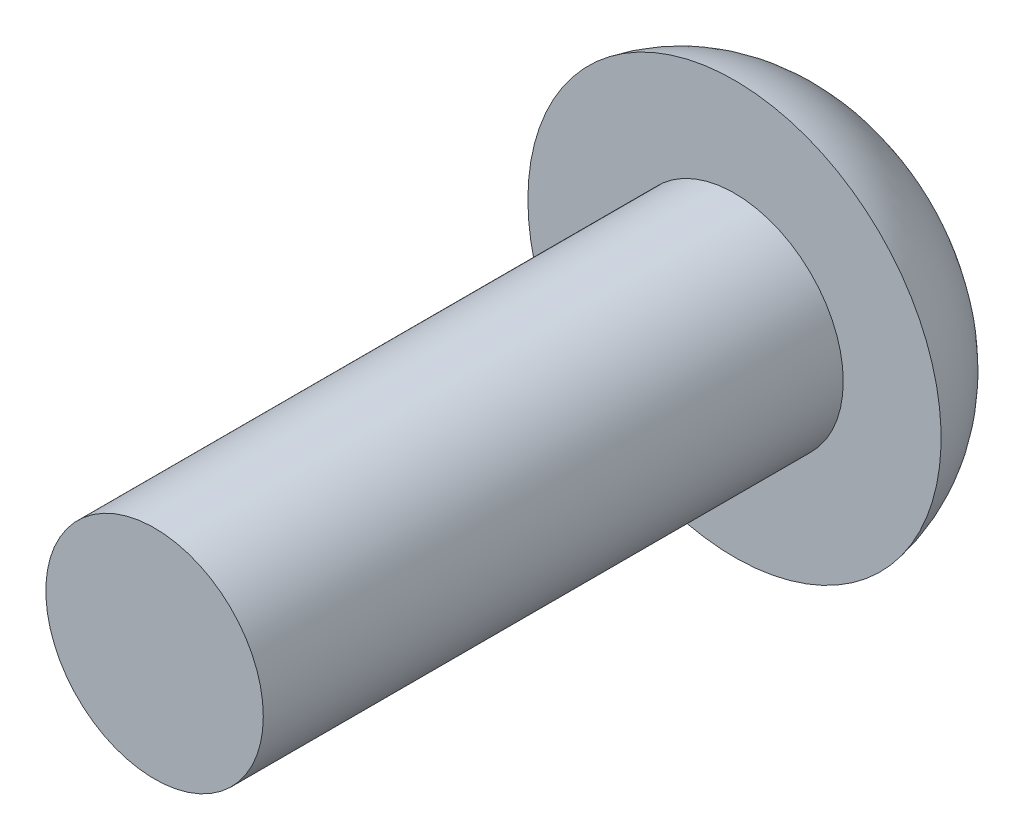
SolidWorks part; units mm, degrees
ref_plane "前视基准面" through (0, 0, 0) normal (0, 0, 1) x (1, 0, 0)
ref_plane "上视基准面" through (0, 0, 0) normal (0, 1, 0) x (1, 0, 0)
ref_plane "右视基准面" through (0, 0, 0) normal (1, 0, 0) x (0, 0, -1)
sketch "草图1" plane through (0, 0, 0) normal (0, 0, 1) x (1, 0, 0)
  circle A0 centre (0, 0) radius 1.5
extrude "凸台-拉伸1" add sketch "草图1" along normal blind 8
sketch "草图2" plane through (0, 0, 0) normal (0, 0, -1) x (-1, 0, 0)
  circle A0 centre (0, 0) radius 2.85
extrude "凸台-拉伸2" add sketch "草图2" along normal blind 1.65
fillet "圆角1" radius 2 1 edges at (-2.85, 0, -1.65)
